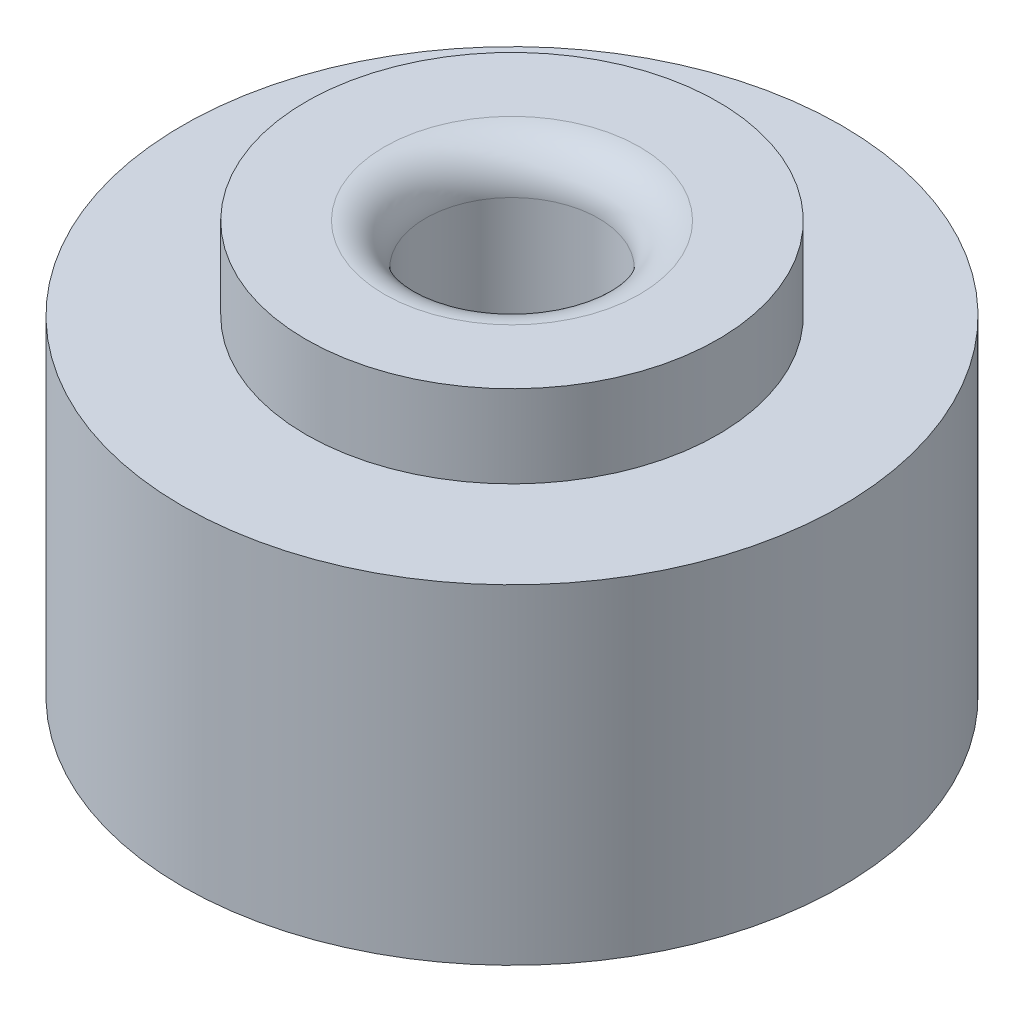
SolidWorks part; units mm, degrees
material "Tin Bearing Bronze"
ref_plane "Front" through (0, 0, 0) normal (0, 0, 1) x (1, 0, 0)
ref_plane "Top" through (0, 0, 0) normal (0, 1, 0) x (1, 0, 0)
ref_plane "Right" through (0, 0, 0) normal (1, 0, 0) x (0, 0, -1)
sketch "Sketch1" plane through (0, 0, 0) normal (0, 1, 0) x (1, 0, 0)
  circle A0 centre (0, 0) radius 4
  circle A1 centre (0, 0) radius 1.05
  dimension "D1" = 8
  dimension "D2" = 2.1
extrude "Boss-Extrude1" add sketch "Sketch1" along normal blind 4
sketch "Sketch2" plane through (0, 4, 0) normal (0, 1, 0) x (1, 0, 0)
  circle A0 centre (0, 0) radius 2.5
  dimension "D1" = 5
extrude "Boss-Extrude2" add sketch "Sketch2" along normal blind 1
extrude "Cut-Extrude1" cut sketch "Sketch1<2>" along normal through all contours A1 region at (0, 0, 0)
sketch "Sketch1<2>" plane through (0, 0, 0) normal (0, 1, 0) x (1, 0, 0) same geometry as "Sketch1"
fillet "Fillet1" radius 0.5 2 edges at (0, 0, 1.05) (0, 5, 1.05)
